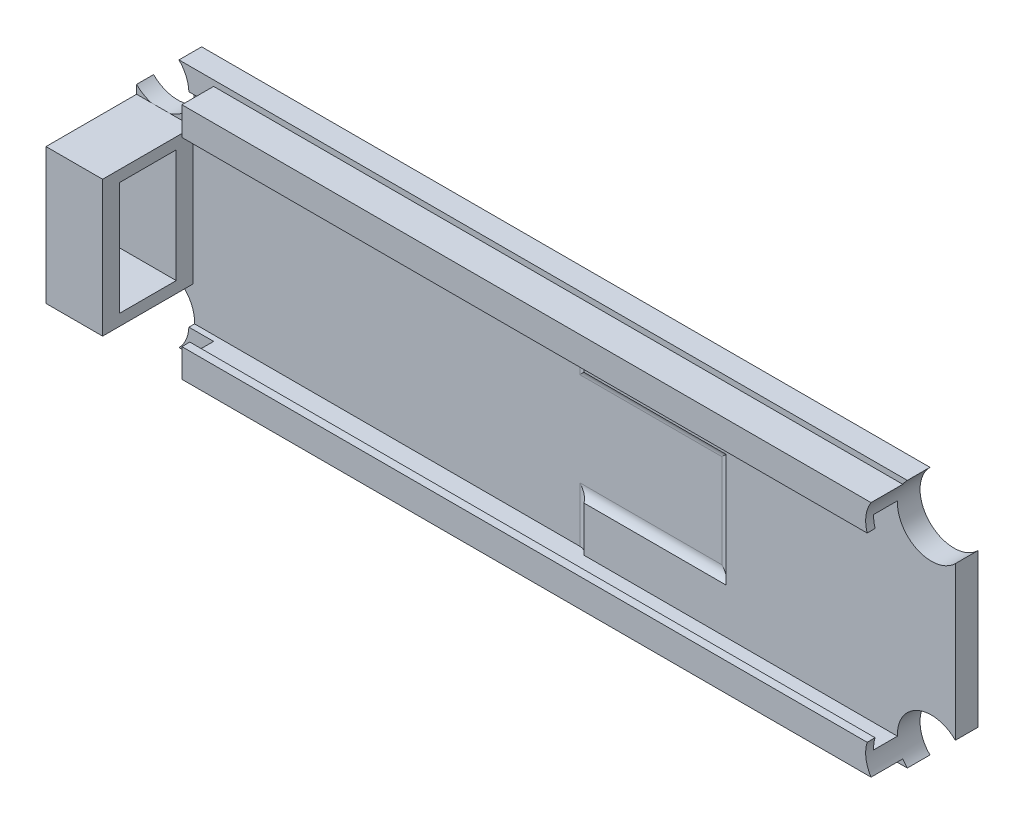
SolidWorks part; units mm, degrees
ref_plane "Ebene vorne" through (0, 0, 0) normal (1, 0, 0) x (0, 1, 0)
ref_plane "Ebene oben" through (0, 0, 0) normal (0, 0, 1) x (0, 1, 0)
ref_plane "Ebene rechts" through (0, 0, 0) normal (0, 1, 0) x (-1, 0, 0)
sketch "Skizze1" plane through (0, 0, 0) normal (0, 0, 1) x (0, 1, 0)
  line L30 (-11, -36.4) -> (11, -36.4)
  line L31 (-11, -36.4) -> (-11, 36.4)
  line L32 (-11, 36.4) -> (11, 36.4)
  line L33 (11, -36.4) -> (11, 36.4)
  line L34 (-11, -36.4) -> (11, 36.4) construction
  line L35 (-11, 36.4) -> (11, -36.4) construction
  point P0 (0, 0)
  dimension "D1" = 22
  dimension "D2" = 72.8
extrude "Aufsatz-Linear austragen1" add sketch "Skizze1" along normal blind 2
sketch "Skizze2" plane through (0, 0, 2) normal (0, 0, 1) x (1, 0, 0)
  line L0 (36.4, 11) -> (-36.4, 11) construction
  circle A0 centre (-34.28, 8.88) radius 3
  circle A1 centre (-34.28, -8.88) radius 3
  circle A2 centre (34.28, -8.88) radius 3
  circle A3 centre (34.28, 8.88) radius 3
  dimension "D3" = 6
  dimension "D6" = 6
  dimension "D9" = 6
  dimension "D12" = 6
  dimension "D1" = 2.12
  dimension "D2" = 2.12
  dimension "D4" = 2.12
  dimension "D5" = 2.12
  dimension "D7" = 2.12
  dimension "D8" = 2.12
  dimension "D10" = 2.12
  dimension "D11" = 2.12
extrude "Schnitt-Linear austragen1" cut sketch "Skizze2" against normal blind 2
sketch "Skizze3" plane through (0, 0, 2) normal (0, 0, 1) x (1, 0, 0)
  line L0 (-36.4, 0) -> (36.4, 0) construction
  line L1 (36.4, -10.5) -> (-29.1, -10.5)
  line L2 (36.4, -10.5) -> (36.4, 10.5)
  line L3 (36.4, 10.5) -> (-29.1, 10.5)
  line L4 (-29.1, -10.5) -> (-29.1, 10.5)
  line L5 (-36.4, 6.7574) -> (-36.4, -6.7574) construction
  line L6 (36.4, -6.7574) -> (36.4, 6.7574) construction
  dimension "D1" = 65.5
  dimension "D2" = 21
extrude "Aufsatz-Linear austragen2" add sketch "Skizze3" along normal blind 2.8
sketch "Skizze4" plane through (-29.1, 0, 0) normal (-1, 0, 0) x (0, -1, 0)
  line L0 (0, 0) -> (0, 2) construction
  line L1 (-8, 4.8) -> (8, 4.8)
  line L2 (-6.7574, 2) -> (6.7574, 2) construction
  line L3 (0, 2) -> (0, 4.8) construction
  line L4 (-10.5, 4.8) -> (10.5, 4.8) construction
  line L15 (-9, 2) -> (9, 2)
  line L16 (-9, 2) -> (-9, 4.1)
  line L17 (-9, 4.1) -> (9, 4.1) construction
  line L18 (9, 2) -> (9, 4.1)
  line L19 (-9, 2) -> (9, 4.1) construction
  line L20 (-9, 4.1) -> (9, 2) construction
  line L21 (-10.5, 4.8) -> (10.5, 4.8) construction
  line L22 (-9, 4.1) -> (-8, 4.1)
  line L23 (-8, 4.1) -> (-8, 4.8)
  line L24 (8, 4.8) -> (8, 4.1)
  line L25 (8, 4.1) -> (9, 4.1)
  point P2 (0, 3.4)
  point P5 (0, 3.05)
  point P6 (0, 3.4)
  point P20 (0, 4.8)
  dimension "D1" = 18
  dimension "D2" = 2.1
  dimension "D3" = 16
extrude "Schnitt-Linear austragen2" cut sketch "Skizze4" against normal through all
sketch "Skizze5" plane through (0, 0, 2) normal (0, 0, -1) x (1, 0, 0)
  line L0 (36.4, -11) -> (36.4, 11) construction
  line L2 (36.4, 6.7574) -> (36.4, -6.7574) construction
  circle A1 centre (34.28, -8.88) radius 3
  circle A2 centre (34.28, 8.88) radius 3
  point P3 (36.4, 0)
  dimension "D4" = 6
  dimension "D7" = 6
  dimension "D1" = 22
  dimension "D2" = 2.12
  dimension "D3" = 2.12
  dimension "D5" = 2.12
  dimension "D6" = 2.12
extrude "Schnitt-Linear austragen4" cut sketch "Skizze5" against normal through all
sketch "Skizze6" plane through (-36.4, 0, 0) normal (-1, 0, 0) x (0, -1, 0)
  line L0 (-6.7574, 2) -> (6.7574, 2) construction
  line L1 (-9, 2.5) -> (9, 2.5)
  line L2 (-9, 2.5) -> (-9, 1.5)
  line L3 (-9, 1.5) -> (9, 1.5)
  line L4 (9, 2.5) -> (9, 1.5)
  line L5 (-9, 2.5) -> (9, 1.5) construction
  line L6 (-9, 1.5) -> (9, 2.5) construction
  point P0 (0, 2)
  dimension "D1" = 18
  dimension "D2" = 1
extrude "Schnitt-Linear austragen5" cut sketch "Skizze6" against normal blind 40
sketch "Skizze8" plane through (0, 0, 2) normal (0, 0, 1) x (1, 0, 0)
  line L0 (1.156, -8) -> (1.156, 8) construction
  line L1 (1.156, -5.0073) -> (16.156, -5.0073)
  line L2 (1.156, -5.0073) -> (1.156, 4.9927)
  line L3 (1.156, 4.9927) -> (16.156, 4.9927)
  line L4 (16.156, -5.0073) -> (16.156, 4.9927)
  line L5 (31.412, -8) -> (-29.1, -8) construction
  line L8 (31.412, 8) -> (-29.1, 8) construction
  dimension "D1" = 10
  dimension "D2" = 15
extrude "Schnitt-Linear austragen6" cut sketch "Skizze8" against normal blind 0.5
fillet "Verrundung3" radius 1 5 edges at (3.6, -7.0037, 1.5) (9.878, -5.0073, 1.5) (3.6, 6.9963, 1.5) (9.878, 4.9927, 1.5) (16.156, -0.0073, 1.5)
sketch "Skizze9" plane through (0, 0, 1.5) normal (0, 0, 1) x (1, 0, 0)
  line L0 (-36.4, 6.7574) -> (-36.4, -6.7574) construction
  line L5 (-31.4, 6) -> (-36.4, 6)
  line L6 (-31.4, 6) -> (-31.4, -6)
  line L7 (-31.4, -6) -> (-36.4, -6)
  line L8 (-36.4, 6) -> (-36.4, -6)
  line L9 (-31.4, 6) -> (-36.4, -6) construction
  line L10 (-31.4, -6) -> (-36.4, 6) construction
  line L11 (-36.4, -6.7574) -> (-36.4, 6.7574) construction
  point P0 (-33.9, 0)
  point P8 (-36.4, 0)
  dimension "D1" = 12
  dimension "D2" = 5
extrude "Aufsatz-Linear austragen3" add sketch "Skizze9" along normal blind 8
sketch "Skizze10" plane through (-36.4, 0, 0) normal (-1, 0, 0) x (0, -1, 0)
  line L1 (-5, 3) -> (5, 3)
  line L2 (-5, 3) -> (-5, 8)
  line L3 (-5, 8) -> (5, 8)
  line L4 (5, 3) -> (5, 8)
  line L5 (-5, 3) -> (5, 8) construction
  line L6 (-5, 8) -> (5, 3) construction
  point P0 (0, 5.5)
  dimension "D1" = 5
  dimension "D2" = 10
  dimension "D3" = 3
extrude "Schnitt-Linear austragen7" cut sketch "Skizze10" against normal through all
